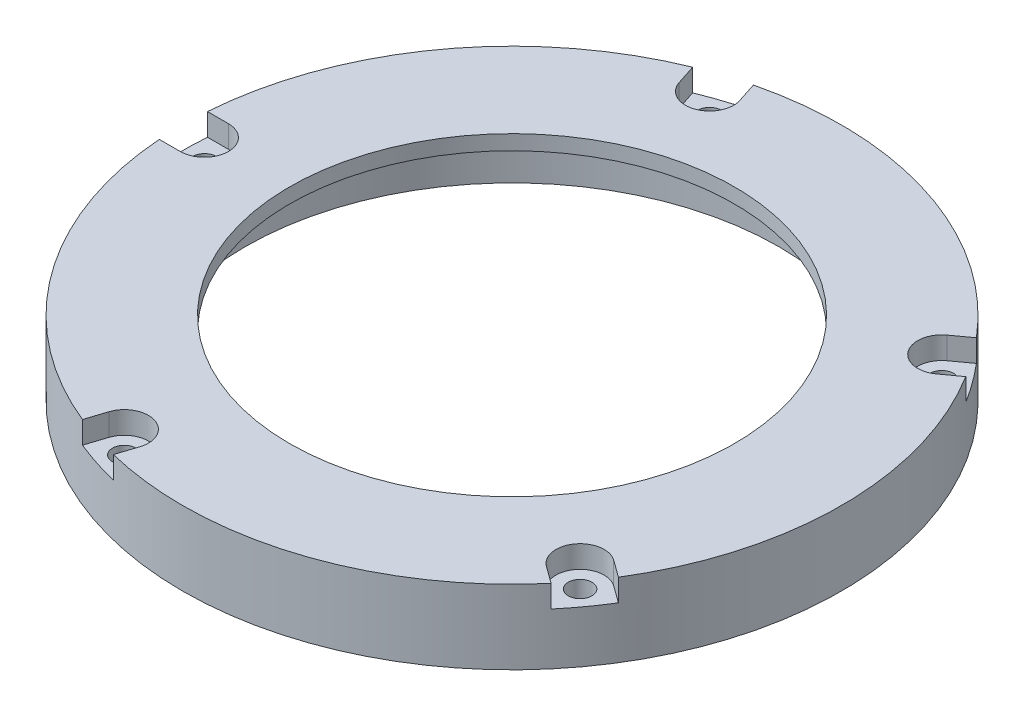
SolidWorks part; units mm, degrees
ref_plane "Front Plane" through (0, 0, 0) normal (0, 0, 1) x (1, 0, 0)
ref_plane "Top Plane" through (0, 0, 0) normal (0, 1, 0) x (1, 0, 0)
ref_plane "Right Plane" through (0, 0, 0) normal (1, 0, 0) x (0, 0, -1)
sketch "Sketch1" plane through (0, 0, 0) normal (0, 1, 0) x (1, 0, 0)
  circle A0 centre (0, 0) radius 44.45
  circle A1 centre (0, 0) radius 36
  circle A2 centre (0, 0) radius 30
  dimension "D1" = 60
  dimension "D2" = 72
  dimension "D3" = 88.9
extrude "Boss-Extrude1" add sketch "Sketch1" against normal blind 2 contours A1 A2 | A0 A1 region at (-43.1928, 0, 0) region at (-34.9818, 0, 0)
extrude "Boss-Extrude2" add sketch "Sketch1<3>" against normal blind 8 from surface contours A0 A1 region at (-43.1928, 0, 0) starting at face at (0, -2, 30)
sketch "Sketch1<3>" plane through (0, 0, 0) normal (0, 1, 0) x (1, 0, 0) same geometry as "Sketch1"
hole_wizard "CBORE for M3 SHCS2" positions "Sketch6" profile "Sketch7" counterbore size "M3" standard "ANSI Metric" end condition through all
sketch "Sketch6" plane through (0, 0, 0) normal (0, 1, 0) x (1, 0, 0)
  line L0 (0, 0) -> (-41.5, 0) construction
  point P2 (-41.5, 0)
  dimension "D1" = 41.5
sketch "Sketch7" plane through (-41.5, 0, 0) normal (1, 0, 0) x (0, 0, 1)
  line L0 (0, 0) -> (0, 10)
  line L1 (0, 10) -> (1.6, 10)
  line L3 (1.6, 10) -> (1.6, 3)
  line L4 (1.6, 3) -> (3.25, 3)
  line L5 (3.25, 3) -> (3.25, 0)
  line L7 (3.25, 0) -> (0, 0)
  line L11 (0, -6.35) -> (0, 107.95) construction
  dimension "Thru Hole Dia." = 3.2
  dimension "Thru Hole Depth" = 10
  dimension "C'Bore Dia." = 6.5
  dimension "C'Bore Depth" = 3
sketch "Sketch8" plane through (0, -3, 0) normal (0, 1, 0) x (1, 0, 0)
  line L1 (-41.5, 3.25) -> (-44.45, 3.25)
  line L2 (-41.5, 3.25) -> (-41.5, -3.25)
  line L3 (-41.5, -3.25) -> (-44.45, -3.25)
  line L4 (-44.45, 3.25) -> (-44.45, -3.25)
  arc A2 (-44.4276, 1.4113) -> (-44.4276, -1.4113) centre (0, 0) ccw
  arc A3 (-44.4276, -1.4113) -> (-44.4276, 1.4113) centre (-41.5, 0) ccw
  arc A4 (-44.4276, 1.4113) -> (-44.4276, -1.4113) centre (0, 0) ccw
  arc A5 (-44.4276, -1.4113) -> (-44.4276, 1.4113) centre (-41.5, 0) ccw
  arc M4 (-44.4276, 1.4113) -> (-44.4276, -1.4113) centre (0, 0) ccw
  arc M5 (-44.4276, -1.4113) -> (-44.4276, 1.4113) centre (-41.5, 0) ccw
  circle M6 centre (-41.5, 0) radius 1.6
  dimension "D1" = 0
extrude "Cut-Extrude1" cut sketch "Sketch8" along normal through all contours L2 M5 M4 M6 | L1 L4 M4 M5 | L4 L3 M4 M5 region at (-43.7661, -3, -2.7196) region at (-41.5714, -3, -2.425) region at (-43.7661, -3, 2.7196)
pattern_circular "CirPattern1" count 5 over 360 about axis through (0, -2, 0) along (0, 1, 0) of "Cut-Extrude1", "CBORE for M3 SHCS2" reverse direction yes
equation "\"Ratio\"= 15"
equation "\"Hull Diameter\"= 3.5in"
equation "\"Fixed Ring Diameter\"= 76"
equation "\"Fixed Pin Diameter\"= 6"
equation "\"Output Ring Diameter\"= 40"
equation "\"Output Pin Diameter\"= 6"
equation "\"Disk Bearing Inner Diameter\"= 9"
equation "\"Disk Bearing Outer Diameter\"= 17"
equation "\"Disk Bearing Height\"= 5"
equation "\"Shaft Bearing Inner Diameter\"= 15"
equation "\"Shaft Bearing Outer Diameter\"= 21"
equation "\"Shaft Bearing Height\"= 4"
equation "\"Eccentricity\"= 1.5"
equation "\"Disk Height\"= 8"
equation "\"Disk Spacing\"= 5"
equation "\"Hull Height\"= 40"
equation "\"Shaft End Bearing Inner Diameter\"= 12"
equation "\"Shaft End Bearing Outer Diameter\"= 18"
equation "\"Shaft End Bearing Height\"= 4"
equation "\"Output Bearing Inner Diameter\"= 55"
equation "\"Output Bearing Outer Diameter\"= 72"
equation "\"Outer Bearing Height\"= 9"
equation "\"D1@Sketch1\"=\"Output Bearing Inner Diameter\"+5"
equation "\"D2@Sketch1\"=\"Output Bearing Outer Diameter\""
equation "\"D3@Sketch1\"=\"Hull Diameter\""
